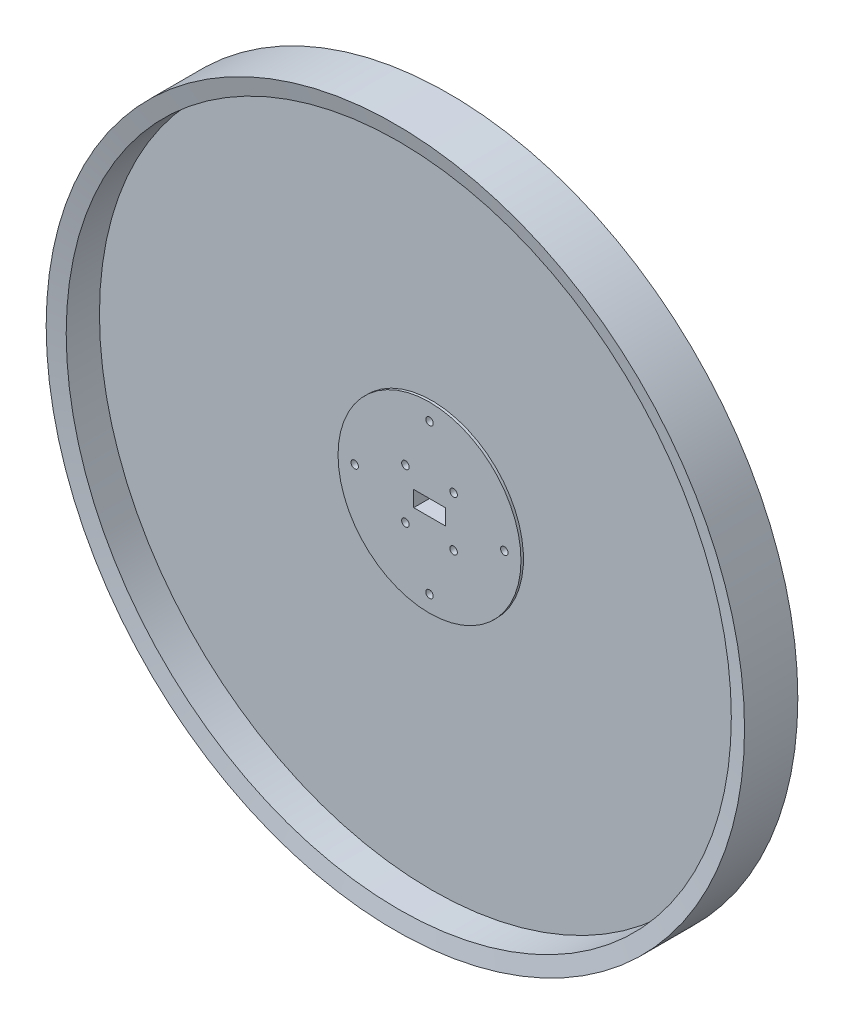
SolidWorks part; units mm, degrees
ref_plane "Спереди" through (0, 0, 0) normal (0, 0, 1) x (1, 0, 0)
ref_plane "Сверху" through (0, 0, 0) normal (0, 1, 0) x (1, 0, 0)
ref_plane "Справа" through (0, 0, 0) normal (1, 0, 0) x (0, 0, -1)
sketch "Эскиз1" plane through (0, 0, 0) normal (0, 1, 0) x (1, 0, 0)
  line L0 (0, 0) -> (200, 0)
  line L6 (210, 10) -> (0, 10)
  line L7 (0, 10) -> (0, 0)
  line L8 (200, 0) -> (200, -20)
  line L9 (200, -20) -> (210, -22.05)
  line L10 (210, -22.05) -> (210, 10)
  parabola Q0 (800, -320) -> (0, 0) focus (0, -500) apex (0, 0) construction
  dimension "D1" = 500
  dimension "D2" = 800
  dimension "D3" = 200
  dimension "D4" = 10
  dimension "D5" = 210
revolve "Повернуть1" add sketch "Эскиз1" angle 360 about L7
sketch "Эскиз2" plane through (0, 0, 0) normal (0, 0, 1) x (1, 0, 0)
  line L1 (-9.5, -4.75) -> (9.5, -4.75)
  line L2 (-9.5, -4.75) -> (-9.5, 4.75)
  line L3 (-9.5, 4.75) -> (9.5, 4.75)
  line L4 (9.5, -4.75) -> (9.5, 4.75)
  line L5 (-9.5, -4.75) -> (9.5, 4.75) construction
  line L6 (-9.5, 4.75) -> (9.5, -4.75) construction
  point P0 (0, 0)
  dimension "D1" = 19
  dimension "D2" = 9.5
extrude "Вырез-Вытянуть1" cut sketch "Эскиз2" against normal through all and the other way through all
sketch "Эскиз3" plane through (0, 0, 0) normal (0, 0, 1) x (1, 0, 0)
  circle A0 centre (0, 0) radius 55
extrude "Бобышка-Вытянуть1" add sketch "Эскиз3" along normal up to surface (1.5125 mm away) contours A0
sketch "Эскиз4" plane through (0, 0, 1.5125) normal (0, 0, 1) x (1, 0, 0)
  line L1 (-9.5, -4.75) -> (9.5, -4.75)
  line L2 (-9.5, -4.75) -> (-9.5, 4.75)
  line L3 (-9.5, 4.75) -> (9.5, 4.75)
  line L4 (9.5, -4.75) -> (9.5, 4.75)
  line L5 (-9.5, -4.75) -> (9.5, 4.75) construction
  line L6 (-9.5, 4.75) -> (9.5, -4.75) construction
  point P0 (0, 0)
  dimension "D1" = 19
  dimension "D2" = 9.5
extrude "Вырез-Вытянуть2" cut sketch "Эскиз4" against normal blind 2
sketch "Эскиз6" plane through (0, 0, 1.5125) normal (0, 0, 1) x (1, 0, 0)
  line L0 (0, 0) -> (0, 45) construction
hole_wizard "Отверстие с зазором M41" positions "Трехмерный эскиз1" profile "Эскиз8" hole size "M4" standard "ISO" end condition through all
sketch3d "Трехмерный эскиз1"
  point P0 (0, 45, 1.5125)
sketch "Эскиз8" plane through (0, 45, 1.5125) normal (1, 0, 0) x (0, -1, 0)
  line L0 (0, 0) -> (0, 11.5125)
  line L1 (0, 11.5125) -> (2.25, 11.5125)
  line L2 (2.25, 11.5125) -> (2.25, 0)
  line L5 (2.25, 0) -> (0, 0)
  line L11 (0, -6.35) -> (0, 107.95) construction
  dimension "Диаметр сквозного отверстия" = 4.5
  dimension "Глубина сквозного отверстия" = 11.5125
ref_axis "Ось1" through (0, 0, 0) along (0, 0, 1)
pattern_circular "Круговой массив1" count 4 every 90 about axis through (0, 0, 0) along (0, 0, 1) of "Отверстие с зазором M41"
sketch "Эскиз9" plane through (0, 0, -10) normal (0, 0, -1) x (-1, 0, 0)
  line L1 (-14.5, -15) -> (14.5, -15) construction
  line L2 (-14.5, -15) -> (-14.5, 15) construction
  line L3 (-14.5, 15) -> (14.5, 15) construction
  line L4 (14.5, -15) -> (14.5, 15) construction
  line L5 (-14.5, -15) -> (14.5, 15) construction
  line L6 (-14.5, 15) -> (14.5, -15) construction
  point P0 (0, 0)
  dimension "D1" = 29
  dimension "D2" = 30
hole_wizard "Отверстие с зазором M42" positions "Трехмерный эскиз2" profile "Эскиз10" hole size "M4" standard "ISO" end condition through all
sketch3d "Трехмерный эскиз2"
  point P0 (-14.5, 15, -10)
  point P4 (14.5, 15, -10)
  point P7 (14.5, -15, -10)
  point P10 (-14.5, -15, -10)
sketch "Эскиз10" plane through (-14.5, 15, -10) normal (1, 0, 0) x (0, 1, 0)
  line L0 (0, 0) -> (0, 32.05)
  line L1 (0, 32.05) -> (2.25, 32.05)
  line L2 (2.25, 32.05) -> (2.25, 0.025)
  line L3 (2.25, 0.025) -> (2.275, 0)
  line L5 (2.275, 0) -> (0, 0)
  line L6 (-2.25, 0.025) -> (-2.275, 0) construction
  line L11 (0, -6.35) -> (0, 107.95) construction
  dimension "Диаметр сквозного отверстия" = 4.5
  dimension "Глубина сквозного отверстия" = 32.05
  dimension "Диаметр передней зенковки" = 4.55
  dimension "Угол передней зенковки" = 90
